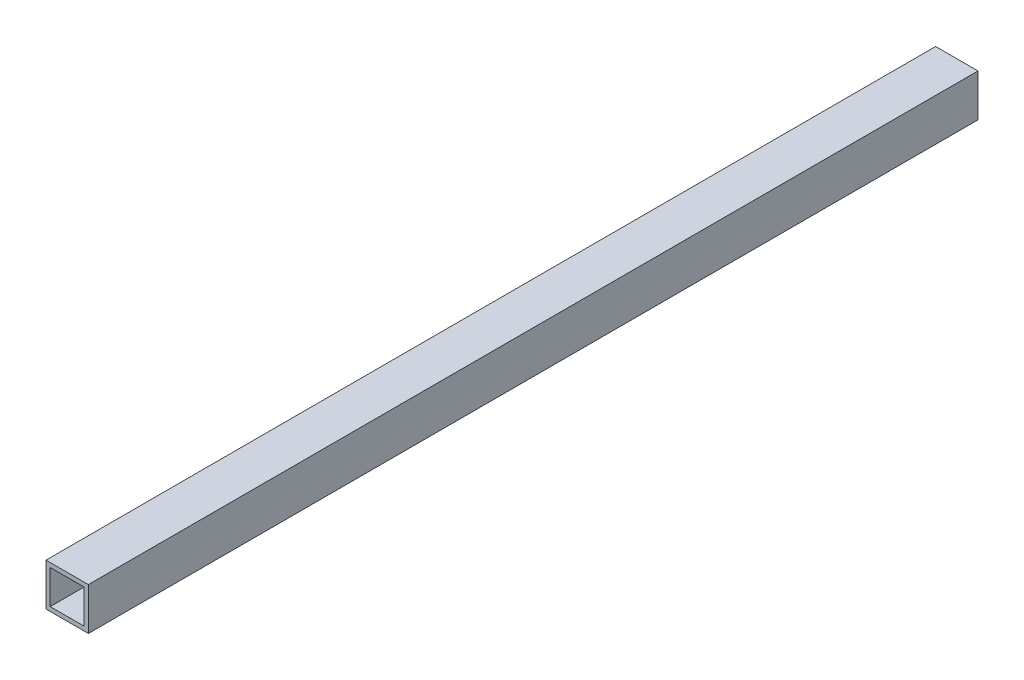
SolidWorks part; units mm, degrees
material "Thornel Mat VMA"
ref_plane "前视基准面" through (0, 0, 0) normal (0, 0, 1) x (1, 0, 0)
ref_plane "上视基准面" through (0, 0, 0) normal (0, 1, 0) x (1, 0, 0)
ref_plane "右视基准面" through (0, 0, 0) normal (1, 0, 0) x (0, 0, -1)
sketch "草图1" plane through (0, 0, 0) normal (0, 0, 1) x (1, 0, 0)
  line L1 (5, 5) -> (-5, 5)
  line L2 (5, 5) -> (5, -5)
  line L3 (5, -5) -> (-5, -5)
  line L4 (-5, 5) -> (-5, -5)
  line L5 (5, 5) -> (-5, -5) construction
  line L6 (5, -5) -> (-5, 5) construction
  line L7 (4, 4) -> (-4, 4)
  line L8 (4, 4) -> (4, -4)
  line L9 (4, -4) -> (-4, -4)
  line L10 (-4, 4) -> (-4, -4)
  line L11 (4, 4) -> (-4, -4) construction
  line L12 (4, -4) -> (-4, 4) construction
  point P0 (0, 0)
  point P6 (0, 0)
  dimension "D1" = 10
  dimension "D2" = 1
extrude "凸台-拉伸1" add sketch "草图1" along normal blind 210
